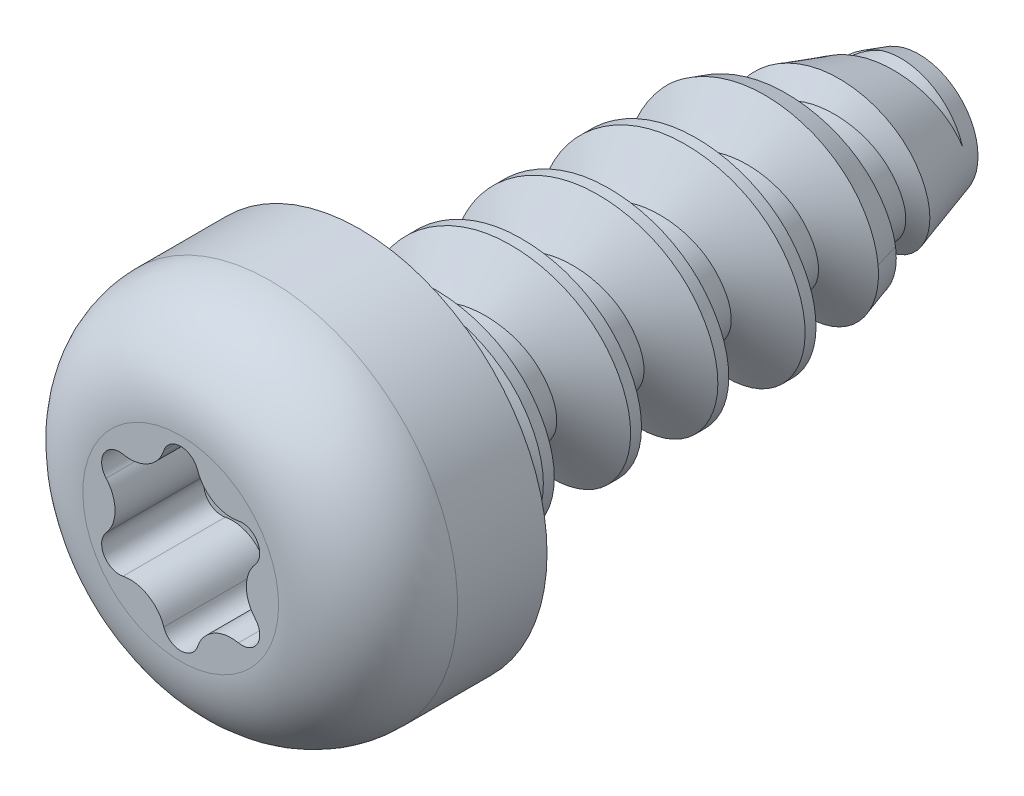
SolidWorks part; units mm, degrees
note: '?' marks a value the reader was unsure of.
ref_plane "Front" through (0, 0, 0) normal (0, 0, 1) x (1, 0, 0)
ref_plane "Top" through (0, 0, 0) normal (0, 1, 0) x (1, 0, 0)
ref_plane "Right" through (0, 0, 0) normal (1, 0, 0) x (0, 0, -1)
sketch "Sketch1" plane through (0, 0, 0) normal (0, 0, 1) x (1, 0, 0)
  circle A0 centre (0, 0) radius 1.675
  dimension "Head Dia" = 3.35
extrude "Extrude3" add sketch "Sketch1" along normal blind 1.6
ref_plane "Plane1" through (0, 0, 1.6) normal (0, 0, 1) x (1, 0, 0)
sketch "Sketch11" plane through (0, 0, 0) normal (1, 0, 0) x (0, 0, -1)
  line L2 (-1.6, 1.675) -> (-1.6, -1.675) construction
  line L4 (0, 1.675) -> (-1.6, 1.675) construction
  line L5 (-0.8, 1.675) -> (-0.8, 1.775)
  line L6 (-0.8, 1.775) -> (-1.7, 1.775)
  line L7 (-1.7, 1.775) -> (-1.7, 0.875)
  line L8 (-1.7, 0.875) -> (-1.6, 0.875)
  line L11 (0, 0) -> (-1.6, 0) construction
  arc A0 (-1.6, 0.875) -> (-0.8, 1.675) centre (-0.8, 0.875) cw
  dimension "D1" = 0.1
  dimension "D2" = 0.1
revolve "Cut-Revolve3" cut sketch "Sketch11" angle 360 about L11
sketch "Sketch14" plane through (0, 0, 0) normal (1, 0, 0) x (0, 0, -1)
  line L0 (0.195, 0.5778) -> (0.4388, 1) construction
  line L2 (0.4388, 1) -> (0.5363, 1)
  line L3 (0.5363, 1) -> (0.78, 0.5778) construction
  line L4 (0.78, 0.5778) -> (0.195, 0.5778) construction
  line L5 (0.78, 0.5778) -> (0.975, 0.5778) construction
  line L6 (0.195, 0.5778) -> (0, 0.5778) construction
  line L10 (0, 1.675) -> (0, -1.675) construction
  line L11 (0.4388, 1) -> (0.195, 0.5778)
  line L12 (0.195, 0.5778) -> (0.78, 0.5778)
  line L13 (0.78, 0.5778) -> (0.5363, 1)
  line L14 (0, 0) -> (-1.6, 0) construction
  line L15 (0, 0) -> (-1.6, 0) construction
  point P11 (0.4875, 1)
  dimension "D1" = 60
  dimension "Pitch" = 0.78
  dimension "D3" = 0.195
  dimension "D4" = 0.0975
  dimension "Screw Dia" = 2
ref_plane "Plane2" through (0, 0, -0.4875) normal (0, 0, 1) x (1, 0, 0)
sketch "Sketch4" plane through (0, 0, 0) normal (1, 0, 0) x (0, 0, -1)
  line L0 (0, 0) -> (5, 0)
  line L2 (5, -0.5778) -> (0, -0.5778) construction
  line L3 (5, 0) -> (5, 0.5778)
  line L4 (5, 0.5778) -> (0, 0.5778)
  line L5 (0, 0) -> (-1.6, 0) construction
  line L6 (0, 0.5778) -> (0, 0)
  line L7 (5, 0) -> (7.54, 0) construction
  line L8 (0.195, 0.5778) -> (0.78, 0.5778) construction
  point P7 (0, 0.5778)
  dimension "Body Length" = 5
  dimension "D1" = 2.54
revolve "Revolve1" add sketch "Sketch4" angle 360 about L7
sketch "Sketch15" plane through (0, 0, -0.4875) normal (0, 0, 1) x (1, 0, 0)
  circle A0 centre (0, 0) radius 1
curve "Helix/Spiral1" pitch 0.78 height 1.17 turns 1.5
sweep "Sweep1" add profiles "Sketch14" path "Helix/Spiral1"
pattern_linear "LPattern3" count 6 spacing 0.78 along (0, 0, -1) count 2 spacing 0.78 along (0, 0, 1) of "Sweep1"
sketch "Sketch13" plane through (0, 0, 0) normal (1, 0, 0) x (0, 0, -1)
  line L0 (5, 0.5278) -> (3.4649, 1)
  line L2 (3.4649, 1) -> (5, 1)
  line L3 (5, 1) -> (5, 0.5278) construction
  line L4 (5, 0.5278) -> (5, 0)
  line L5 (0, 0) -> (5, 0) construction
  line L6 (0.4388, 1) -> (0.5363, 1) construction
  line L7 (6.56, 0) -> (6.56, 1)
  line L8 (6.56, 1) -> (5, 1)
  line L9 (5, 0) -> (6.56, 0)
  dimension "D3" = 1.56
  dimension "D1" = 17.097
  dimension "D2" = 0.05
revolve "Cut-Revolve4" cut sketch "Sketch13" angle 360 about L5
sketch "Sketch12" plane through (0, 0, 1.6) normal (0, 0, 1) x (1, 0, 0)
  line L0 (0, 0) -> (0, 0.7914) construction
  line L1 (-0.2935, 0.5084) -> (0, 0)
  line L2 (0, 0) -> (0.2935, 0.5084)
  arc A0 (-0.2935, 0.5084) -> (-0.1509, 0.6829) centre (-0.4526, 0.784) ccw
  arc A1 (-0.1509, 0.6829) -> (0.1509, 0.6829) centre (0, 0.6323) cw
  arc A2 (0.1509, 0.6829) -> (0.2935, 0.5084) centre (0.4526, 0.784) ccw
  circle A5 centre (0, 0) radius 0.7914 construction
  dimension "M" = 1.5829
  dimension "D2" = 0.1591
  dimension "D3" = 0.3183
  dimension "D1" = 60
ref_axis "Axis1" through (0, 0, 1.6) along (0, 0, -1)?
extrude "Cut-Extrude1" cut sketch "Sketch12" against normal blind 0.9143
pattern_circular "CirPattern1" count 6 every 60 about axis through (0, 0, 0) along (0, 0, 1) of "Cut-Extrude1"
sketch "Sketch16" plane through (0, 0, 0) normal (1, 0, 0) x (0, 0, -1)
  line L0 (5, 1) -> (5, -1) construction
  point P0 (-1.6, 0.875)
  point P1 (0, 1.675)
  point P3 (3.4649, -1)
equation "\"D3@LPattern3\"=\"Pitch@Sketch14\""
equation "\"D1@LPattern3\"=(\"Body Length@Sketch4\"/\"Pitch@Sketch14\")"
equation "\"D1@Cut-Extrude1\"=\"Head Ht@Extrude3\"*2/3.5"
equation "\"D3@Sketch14\" = \"Pitch@Sketch14\"/4"
equation "\"D4@Sketch14\" = \"Pitch@Sketch14\"/8"
equation "\"D4@LPattern3\" = \"D3@LPattern3\""
equation "\"D4@Helix/Spiral1\" = \"Pitch@Sketch14\""
equation "\"D2@Sketch12\" = \"Head Dia@Sketch1\" * .0475"
equation "\"D3@Sketch12\" = \"Head Dia@Sketch1\" * .095"
equation "\"M@Sketch12\" = \"Head Dia@Sketch1\" * 0.4725"
equation "\"D3@Sketch13\" = \"D4@Helix/Spiral1\" * 2"
